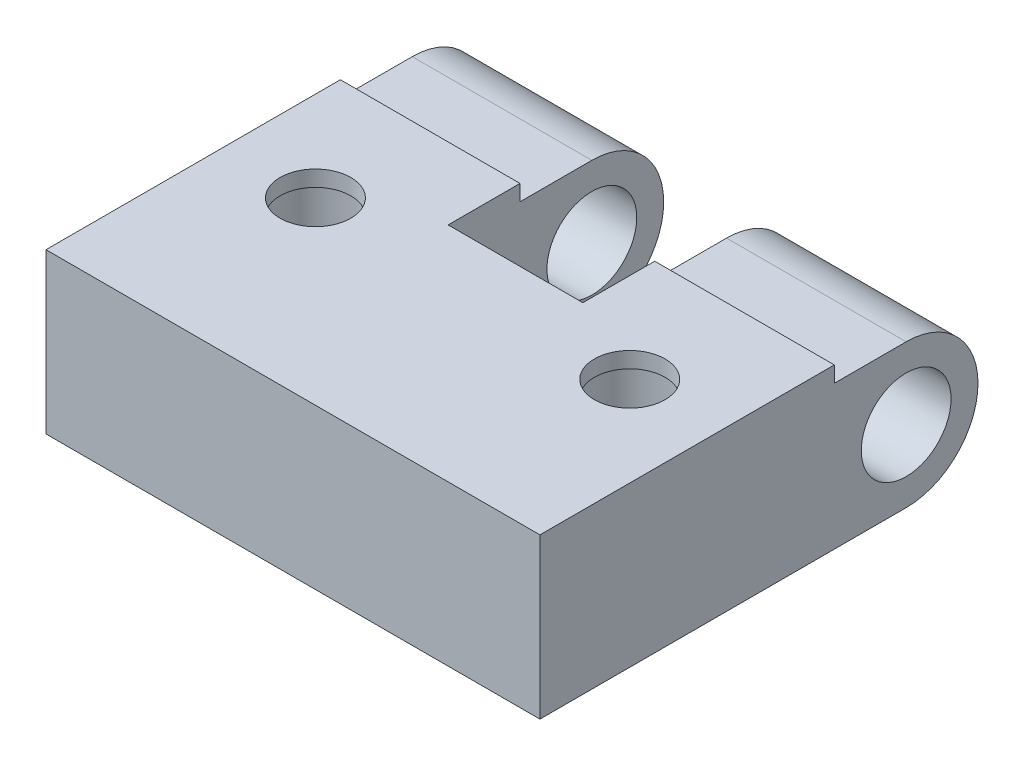
SolidWorks part; units mm, degrees
ref_plane "Front" through (0, 0, 0) normal (0, 0, 1) x (1, 0, 0)
ref_plane "Top" through (0, 0, 0) normal (0, 1, 0) x (1, 0, 0)
ref_plane "Right" through (0, 0, 0) normal (1, 0, 0) x (0, 0, -1)
sketch "Sketch2" plane through (0, 0, 0) normal (1, 0, 0) x (0, 0, -1)
  line L0 (0, 5.08) -> (0, 0)
  line L1 (0, 0) -> (13.1956, 0)
  line L2 (0, 0) -> (0, 5.08)
  line L3 (0, 5.08) -> (13.1956, 5.08)
  line L4 (13.1956, 0) -> (13.1956, 5.08)
  line L5 (0, 5.08) -> (-6.35, 5.08)
  line L6 (0, 0) -> (-6.35, 0)
  line L7 (-6.35, 5.08) -> (-6.35, 0)
  circle A0 centre (6.5978, 2.54) radius 1.5875
  arc A1 (6.5978, 5.08) -> (6.5978, 0) centre (6.5978, 2.54) cw
  point P7 (6.5978, 5.08)
  point P8 (6.5978, 0)
  dimension "D1" = 5.08
  dimension "D2" = 6.35
extrude "Boss-Extrude1" add sketch "Sketch2" along normal blind 6.35 contours L5 L7 L6 L0 | A1 L3 L0 L1 A0 region at (0, 2.54, -3.8093) region at (0, 2.54, 3.175)
sketch "Sketch3" plane through (0, 5.08, 0) normal (0, 1, 0) x (1, 0, 0)
  line L0 (3.175, -6.35) -> (3.175, 0)
  line L1 (6.35, -6.35) -> (0, -6.35) construction
  circle A0 centre (3.175, 0) radius 1.5
  dimension "D1" = 6.35
extrude "Cut-Extrude1" cut sketch "Sketch3" against normal blind 10 contours A0 region at (4.2057, 5.08, 1.0307)
sketch "Sketch4" plane through (6.35, 0, 0) normal (1, 0, 0) x (0, 0, -1)
  line L0 (6.5978, 2.54) -> (2.6291, 2.54)
  line L1 (6.5978, 2.54) -> (1.5178, 2.54)
  line L2 (6.5978, 0) -> (-6.35, 0) construction
  line L3 (1.5178, 0) -> (-6.35, 0)
  line L4 (1.5178, 0) -> (1.5178, 5.08)
  line L5 (1.5178, 5.08) -> (-6.35, 5.08)
  line L6 (-6.35, 0) -> (-6.35, 5.08)
  line M2 (6.5978, 5.08) -> (-6.35, 5.08)
  line M3 (-6.35, 5.08) -> (-6.35, 0)
  line M4 (-6.35, 0) -> (6.5978, 0)
  dimension "D1" = 3.9688
  dimension "D2" = 5.08
extrude "Boss-Extrude2" add sketch "Sketch4" along normal blind 4.7625 contours L4 M4 M2 M3 region at (6.35, 2.54, 2.4161)
ref_plane "Plane1" through (8.7313, 0, 0) normal (1, 0, 0) x (0, 0, -1)
mirror "Mirror1" about plane through (8.7313, 0, 0) normal (1, 0, 0) of "Cut-Extrude1", "Boss-Extrude1"
sketch "Sketch6" plane through (0, 5.08, 0) normal (0, 1, 0) x (1, 0, 0)
  line L0 (6.35, 4.0578) -> (0, 4.0578)
  line L1 (6.35, 6.5978) -> (6.35, 1.5178) construction
  line L2 (0, 6.5978) -> (0, -6.35) construction
  line L3 (0, 4.0578) -> (0, -6.35)
  line L4 (0, -6.35) -> (17.4625, -6.35)
  line L5 (17.4625, -6.35) -> (17.4625, 4.0578)
  line L6 (17.4625, 6.5978) -> (17.4625, -6.35) construction
  line L7 (17.4625, 4.0578) -> (11.1125, 4.0578)
  line L8 (11.1125, 6.5978) -> (11.1125, 1.5178) construction
  line L9 (11.1125, 4.0578) -> (11.1125, 1.5178)
  line L10 (11.1125, 1.5178) -> (6.35, 1.5178)
  line L11 (6.35, 1.5178) -> (6.35, 4.0578)
extrude "Boss-Extrude3" add sketch "Sketch6" along normal blind 0.5625
sketch "Sketch7" plane through (0, 5.08, 0) normal (0, -1, 0) x (1, 0, 0)
  circle A0 centre (14.2875, 0) radius 1.25
  circle A1 centre (3.175, 0) radius 1.25
extrude "Cut-Extrude2" cut sketch "Sketch7" against normal through all
